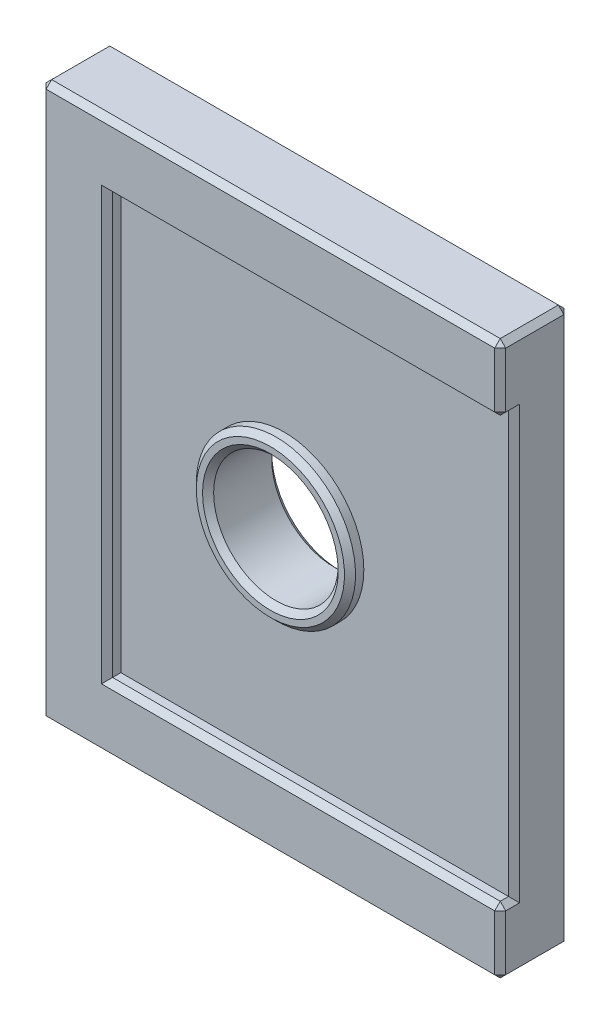
SolidWorks part; units mm, degrees
ref_plane "Front" through (0, 0, 0) normal (0, 0, 1) x (1, 0, 0)
ref_plane "Top" through (0, 0, 0) normal (0, 1, 0) x (1, 0, 0)
ref_plane "Right" through (0, 0, 0) normal (1, 0, 0) x (0, 0, -1)
sketch "Sketch1" plane through (0, 0, 0) normal (0, 0, 1) x (1, 0, 0)
  line L0 (10.1535, 7.5) -> (-5.8, 7.5) construction
  line L1 (-8.3, 10) -> (8.3, 10)
  line L2 (-8.3, 10) -> (-8.3, -10)
  line L3 (-8.3, -10) -> (8.3, -10)
  line L4 (8.3, 10) -> (8.3, -10)
  line L5 (-8.3, 10) -> (8.3, -10) construction
  line L6 (-8.3, -10) -> (8.3, 10) construction
  line L7 (-5.8, 7.5) -> (-5.8, -7.5) construction
  circle A2 centre (0, 0) radius 2.875
  circle A3 centre (0, 0) radius 2.875 construction
  point P0 (0, 0)
  point P5 (-7.3831, 9.3667)
  dimension "D1" = 2.5
  dimension "D2" = 2.5
  dimension "D3" = 0.2
extrude "Boss-Extrude1" add sketch "Sketch1" against normal blind 2
sketch "Sketch2" plane through (0, 0, 0) normal (0, 0, 1) x (1, 0, 0)
  line L0 (8.3, 10) -> (-8.3, 10)
  line L1 (-8.3, 10) -> (-8.3, -10)
  line L2 (-8.3, -10) -> (8.3, -10)
extrude "Extrude-Thin1" add sketch "Sketch2" along normal blind 0.5 thin thin type one direction reverse wall 2.4
sketch "Sketch3" plane through (0, 0, 0) normal (0, 0, 1) x (1, 0, 0)
  circle A0 centre (0, 0) radius 2.875 construction
  circle A1 centre (0, 0) radius 2.875
extrude "Boss-Extrude2" add sketch "Sketch3" along normal up to surface (0.5 mm away) up to face at (0.6, 0, 0.5)
sketch "Sketch4" plane through (0, 0, -2) normal (0, 0, -1) x (-1, 0, 0)
  point P0 (0, 0)
hole_wizard "M4 Clearance Hole1" positions "Sketch4" profile "Sketch5" hole size "M4" standard "ANSI Metric" end condition through all
sketch "Sketch5" plane through (0, 0, -2) normal (1, 0, 0) x (0, 1, 0)
  line L0 (0, 0) -> (0, 2.5)
  line L1 (0, 2.5) -> (2.25, 2.5)
  line L2 (2.25, 2.5) -> (2.25, 0)
  line L5 (2.25, 0) -> (0, 0)
  line L11 (0, -6.35) -> (0, 107.95) construction
  dimension "Thru Hole Dia." = 4.5
  dimension "Thru Hole Depth" = 2.5
chamfer "Deburs" distance 0.2 angle 45 22 edges at (-2.875, 0, 0.5) (-2.25, 0, 0.5) (-8.3, 10, -0.75) (-8.3, -10, -0.75) (8.3, 7.6, 0.25) (8.3, 10, -0.75) (8.3, 0, 0) (8.3, -7.6, 0.25) (-8.3, 0, 0.5) (0, 10, 0.5) (8.3, 8.8, 0.5) (1.2, 7.6, 0.5) (-5.9, 0, 0.5) (1.2, -7.6, 0.5) (8.3, -8.8, 0.5) (0, -10, 0.5) (8.3, -10, -0.75) (0, 10, -2) (-8.3, 0, -2) (0, -10, -2) (8.3, 0, -2) (-2.25, 0, -2)
